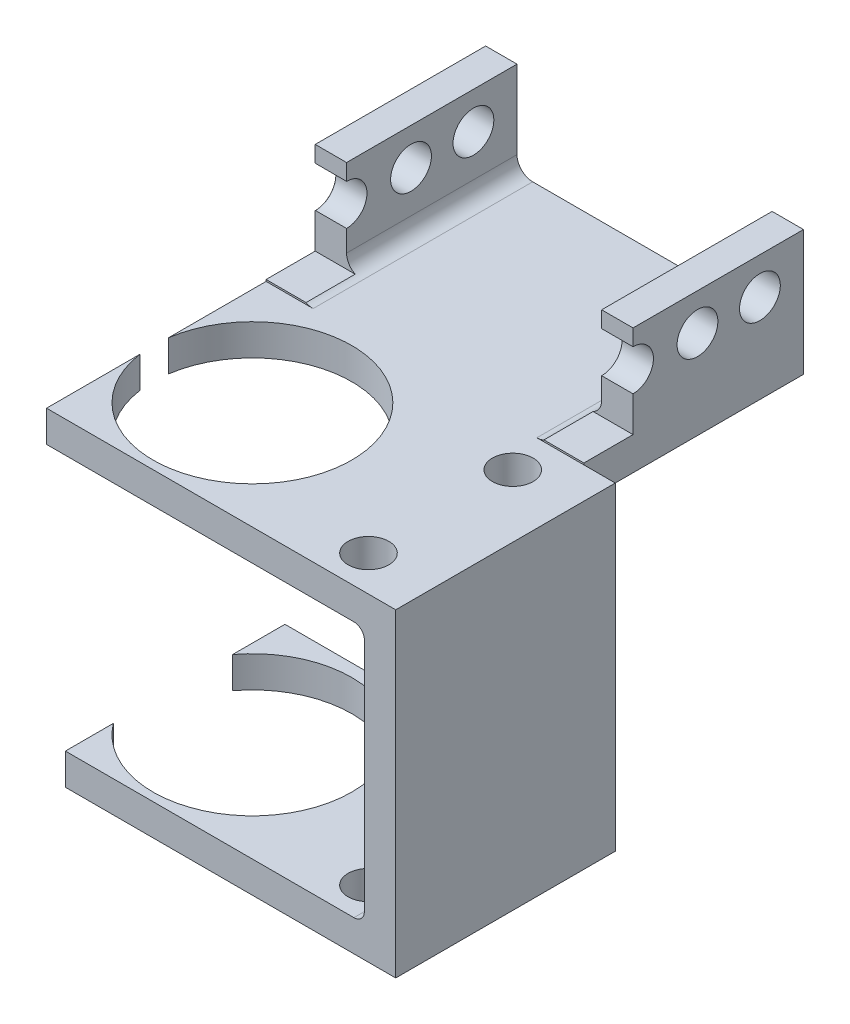
SolidWorks part; units mm, degrees
ref_plane "Front Plane" through (0, 0, 0) normal (0, 0, 1) x (1, 0, 0)
ref_plane "Top Plane" through (0, 0, 0) normal (0, 1, 0) x (1, 0, 0)
ref_plane "Right Plane" through (0, 0, 0) normal (1, 0, 0) x (0, 0, -1)
sketch "Sketch1" plane through (0, 0, 0) normal (0, 0, 1) x (1, 0, 0)
  line L2 (11.421, -21) -> (14.421, -21)
  line L3 (11.421, -21) -> (11.421, -30)
  line L5 (14.421, -21) -> (14.421, -33)
  line L6 (14.3773, -33) -> (14.421, -33)
  line L7 (11.421, -30) -> (-12.979, -30)
  line L12 (-15.979, -33) -> (-15.979, -21)
  line L13 (-15.979, -21) -> (-12.979, -21)
  line L14 (-12.979, -30) -> (-12.979, -21)
  line L16 (14.421, -33) -> (-15.979, -33)
  line L21 (-11.479, -27) -> (-8.779, -27) construction
  line L28 (14.421, -21) -> (14.421, -33)
  line L31 (-12.979, -30) -> (-15.979, -30)
  line L32 (11.421, -30) -> (14.421, -30)
  line L35 (11.021, -23.0865) -> (11.021, 5.0365) construction
  line L36 (-12.979, -23.0865) -> (-12.979, 5.0365) construction
  dimension "D1" = 3
  dimension "D2" = 3
  dimension "D3" = 3
  dimension "D4" = 0.4
  dimension "D5" = 9
  dimension "D7" = 3
extrude "Boss-Extrude1" add sketch "Sketch1" against normal blind 21 contours L32 L7 L31 L12 L16 L6 L28 | L31 L14 L13 L12 | L3 L32 L5 L2 region at (12.921, -25.5, 0) region at (-0.779, -31.5, 0) region at (-14.479, -25.5, 0)
extrude "Boss-Extrude2" add sketch "Sketch1<3>" along normal blind 21 contours L32 L7 L31 L12 L16 L6 L28 region at (-0.779, -31.5, 0)
sketch "Sketch1<3>" plane through (0, 0, 0) normal (0, 0, 1) x (1, 0, 0) same geometry as "Sketch1"
sketch "Sketch5" plane through (0, 0, 21) normal (0, 0, 1) x (1, 0, 0)
  line L0 (14.421, -30) -> (17.421, -30)
  line L1 (17.421, -30) -> (17.421, -60.5)
  line L2 (17.421, -60.5) -> (-14.176, -60.5)
  line L3 (-14.176, -60.5) -> (-14.176, -57.5)
  line L4 (-14.176, -57.5) -> (14.421, -57.5)
  line L5 (14.421, -57.5) -> (14.421, -30)
  line L6 (14.421, -33) -> (-15.979, -33) construction
  dimension "D1" = 3
  dimension "D2" = 3
  dimension "D3" = 24.5
extrude "Boss-Extrude3" add sketch "Sketch5" against normal blind 21
sketch "Sketch6" plane through (0, -60.5, 0) normal (0, -1, 0) x (1, 0, 0)
  line L0 (9.0704, -4.9651) -> (37.4704, -4.9651) construction
  line L1 (17.421, 0) -> (17.421, 21) construction
  circle A0 centre (-6.579, 10.7072) radius 9.5
  dimension "D1" = 24
extrude "Cut-Extrude1" cut sketch "Sketch6" against normal through all both and the other way through all
hole_wizard "M3.5 Clearance Hole1" positions "Sketch7" profile "Sketch8" hole size "M3.5" standard "ANSI Metric" end condition through all
sketch "Sketch7" plane through (0, -60.5, 0) normal (0, -1, 0) x (-1, 0, 0)
  line L0 (6.579, -10.7072) -> (-24.9882, -10.7072) construction
  arc A0 (14.176, -5.0031) -> (14.176, -16.4112) centre (6.579, -10.7072) ccw construction
  arc A1 (14.176, -5.0031) -> (14.176, -16.4112) centre (6.579, -10.7072) ccw
  point P0 (-11.421, -17.6072)
  point P14 (-11.421, -3.8072)
  dimension "D1" = 18
  dimension "D2" = 6.9
sketch "Sketch8" plane through (11.421, -60.5, 17.6072) normal (1, 0, 0) x (0, 0, -1)
  line L0 (0, 0) -> (0, 39.5)
  line L1 (0, 39.5) -> (1.95, 39.5)
  line L2 (1.95, 39.5) -> (1.95, 0.025)
  line L3 (1.95, 0.025) -> (1.975, 0)
  line L5 (1.975, 0) -> (0, 0)
  line L6 (-1.95, 0.025) -> (-1.975, 0) construction
  line L11 (0, -6.35) -> (0, 107.95) construction
  dimension "Thru Hole Dia." = 3.9
  dimension "Thru Hole Depth" = 39.5
  dimension "Near C'Sink Dia." = 3.95
  dimension "Near C'Sink Angle" = 90
fillet "Fillet1" radius 1 2 edges at (14.421, -33, 10.5) (14.421, -57.5, 10.5)
ref_plane "Plane1" through (0, 0, 10) normal (0, 0, -1) x (-1, 0, 0)
sketch "Sketch14" plane through (0, 0, 10) normal (0, 0, -1) x (-1, 0, 0)
  line L0 (-14.421, -45.25) -> (-11.421, -33)
  line L1 (-14.421, -34) -> (-14.421, -56.5) construction
  line L3 (-14.421, -33) -> (15.979, -33) construction
  line L4 (-14.421, -45.25) -> (0.3314, -45.25) construction
  dimension "D1" = 3
rib "Rib16" sketch "Sketch14" sketch "Sketch14" thickness 2 extrusion direction parallel to sketch draft on no parameters "D1"=2
sketch "Sketch16" plane through (0, 0, 10) normal (0, 0, 1) x (1, 0, 0)
  line L0 (14.421, -45.25) -> (11.421, -57.5)
  line L2 (13.421, -57.5) -> (-14.176, -57.5) construction
  line L4 (14.421, -34) -> (14.421, -56.5) construction
  dimension "D1" = 3
rib "Rib17" sketch "Sketch16" sketch "Sketch16" thickness 2 extrusion direction parallel to sketch draft on no parameters "D1"=2
hole_wizard "M3.5 Clearance Hole3" positions "Sketch17" profile "Sketch18" hole size "M3.5" standard "ANSI Metric" end condition through all
sketch "Sketch17" plane through (-15.979, 0, 0) normal (-1, 0, 0) x (0, 0, 1)
  point P0 (-16.8333, -24.5115)
  point P2 (-10.8622, -24.5115)
  point P4 (-4.698, -24.5115)
sketch "Sketch18" plane through (-15.979, -24.5115, -16.8333) normal (0, 1, 0) x (0, 0, 1)
  line L0 (0, 0) -> (0, 33.4)
  line L1 (0, 33.4) -> (1.95, 33.4)
  line L2 (1.95, 33.4) -> (1.95, 0.025)
  line L3 (1.95, 0.025) -> (1.975, 0)
  line L5 (1.975, 0) -> (0, 0)
  line L6 (-1.95, 0.025) -> (-1.975, 0) construction
  line L11 (0, -6.35) -> (0, 107.95) construction
  dimension "Thru Hole Dia." = 3.9
  dimension "Thru Hole Depth" = 33.4
  dimension "Near C'Sink Dia." = 3.95
  dimension "Near C'Sink Angle" = 90
sketch "Sketch19" plane through (14.421, 0, 0) normal (1, 0, 0) x (0, 0, -1)
  line L1 (0, -21) -> (4.698, -21)
  line L2 (0, -21) -> (0, -29.8385)
  line L3 (0, -29.8385) -> (4.698, -29.8385)
  line L4 (4.698, -21) -> (4.698, -29.8385)
  circle A0 centre (4.698, -24.5115) radius 1.95 construction
  circle A1 centre (4.698, -24.5115) radius 1.95 construction
  point P5 (-0.3948, -27.5167)
  point P6 (-0.3948, -29.8385)
  point P7 (0, -21)
  point P10 (0, 0)
  point P11 (3.7711, -21)
  point P15 (0, 0)
extrude "Cut-Extrude2" cut sketch "Sketch19" against normal through all
fillet "Fillet2" radius 1.5 2 edges at (11.421, -30, -10.5) (-12.979, -30, -10.5)
